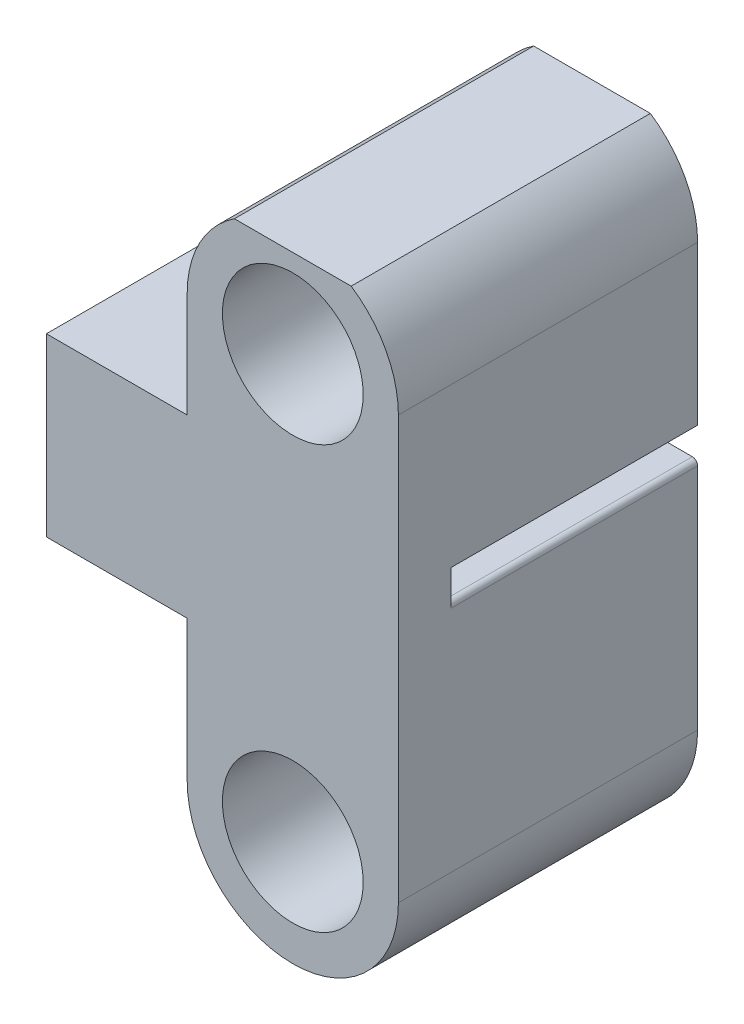
SolidWorks part; units mm, degrees
ref_plane "Front Plane" through (0, 0, 0) normal (0, 0, 1) x (1, 0, 0)
ref_plane "Top Plane" through (0, 0, 0) normal (0, 1, 0) x (1, 0, 0)
ref_plane "Right Plane" through (0, 0, 0) normal (1, 0, 0) x (0, 0, -1)
sketch "Sketch1" plane through (0, 0, 0) normal (0, 0, 1) x (1, 0, 0)
  line L0 (0, 0) -> (0, -12) construction
  line L1 (-3, 0) -> (-3, -12)
  line L2 (3, 0) -> (3, -12)
  arc A0 (3, 0) -> (-3, 0) centre (0, 0) ccw
  arc A1 (-3, -12) -> (3, -12) centre (0, -12) ccw
  circle A2 centre (0, 0) radius 2
  circle A3 centre (0, -12) radius 2
  dimension "D2" = 6
  dimension "D6" = 4
  dimension "D7" = 4
  dimension "D1" = 12
extrude "Boss-Extrude1" add sketch "Sketch1" along normal blind 8.5
sketch "Sketch2" plane through (3, 0, 0) normal (1, 0, 0) x (0, 0, -1)
  line L0 (-8.5, -6) -> (0, -6) construction
  line L1 (-8.5, -12) -> (-8.5, 0) construction
  line L2 (0, -12) -> (0, 0) construction
  line L3 (-4.25, 0) -> (-4.25, -12) construction
  line L4 (-8.5, 0) -> (0, 0) construction
  line L5 (-8.5, -12) -> (0, -12) construction
  circle A0 centre (-4.25, -8.5) radius 2
  dimension "D1" = 4
  dimension "D2" = 2.5
extrude "Cut-Extrude1" [suppressed] cut sketch "Sketch2" against normal through all
sketch "Sketch3" [suppressed] plane through (3, 0, 0) normal (1, 0, 0) x (0, 0, -1)
  line L1 (-0.6416, -8.5) -> (-2.4458, -5.375)
  line L2 (-2.4458, -5.375) -> (-6.0542, -5.375)
  line L3 (-6.0542, -5.375) -> (-7.8584, -8.5)
  line L4 (-7.8584, -8.5) -> (-6.0542, -11.625)
  line L5 (-6.0542, -11.625) -> (-2.4458, -11.625)
  line L6 (-2.4458, -11.625) -> (-0.6416, -8.5)
  line L7 (-1.8684, -4.375) -> (-6.6316, -4.375)
  line L8 (-6.6316, -4.375) -> (-9.0131, -8.5)
  line L9 (-9.0131, -8.5) -> (-6.6316, -12.625)
  line L10 (-6.6316, -12.625) -> (-1.8684, -12.625)
  line L11 (-1.8684, -12.625) -> (0.5131, -8.5)
  line L12 (0.5131, -8.5) -> (-1.8684, -4.375)
  circle A0 centre (-4.25, -8.5) radius 3.125 construction
  circle A1 centre (-4.25, -8.5) radius 4.125 construction
  dimension "D1" = 6.25
  dimension "D2" = 1
extrude "Boss-Extrude2" [suppressed] add sketch "Sketch3" along normal blind 2 and the other way blind 0.5
sketch "Sketch4" [suppressed] plane through (-3, 0, 0) normal (-1, 0, 0) x (0, 0, 1)
  line L0 (4.25, 0) -> (4.25, -6.5) construction
  line L1 (8.5, 0) -> (0, 0) construction
  line L3 (0.75, -2.75) -> (7.75, -2.75)
  line L4 (0.75, -2.75) -> (0.75, -5.75)
  line L5 (0.75, -5.75) -> (7.75, -5.75)
  line L6 (7.75, -2.75) -> (7.75, -5.75)
  line L7 (0.75, -2.75) -> (7.75, -5.75) construction
  line L8 (0.75, -5.75) -> (7.75, -2.75) construction
  circle A0 centre (4.25, -8.5) radius 2 construction
  point P7 (4.25, -4.25)
  dimension "D1" = 7
  dimension "D2" = 3
  dimension "D3" = 2.75
extrude "Cut-Extrude2" [suppressed] cut sketch "Sketch4" against normal through all
sketch "Sketch5" plane through (-3, 0, 0) normal (-1, 0, 0) x (0, 0, 1)
  line L0 (4.25, 0) -> (4.25, -12) construction
  line L1 (8.5, 0) -> (0, 0) construction
  line L2 (8.5, -12) -> (0, -12) construction
  line L3 (0, -6) -> (8.5, -6) construction
  line L4 (0, 0) -> (0, -12) construction
  line L5 (8.5, 0) -> (8.5, -12) construction
  line L7 (0, -15) -> (8.5, -15)
  line L8 (0, -15) -> (0, 3)
  line L9 (0, 3) -> (8.5, 3)
  line L10 (8.5, -15) -> (8.5, 3)
  line L11 (0, -15) -> (8.5, 3) construction
  line L12 (0, 3) -> (8.5, -15) construction
  point P12 (4.25, -6)
extrude "Cut-Extrude3" [suppressed] cut sketch "Sketch5" against normal through all flip side to cut
sketch "Sketch9" plane through (-3, 0, 0) normal (-1, 0, 0) x (0, 0, 1)
  line L0 (8.5, 0) -> (8.5, -12) construction
  line L1 (0, -3) -> (8.5, -3)
  line L2 (0, -3) -> (0, -8)
  line L3 (0, -8) -> (8.5, -8)
  line L4 (8.5, -3) -> (8.5, -8)
  line L5 (0, 0) -> (0, -12) construction
  line L6 (8.5, 0) -> (0, 0) construction
  dimension "D1" = 5
  dimension "D2" = 3
extrude "Boss-Extrude4" add sketch "Sketch9" along normal blind 4
sketch "Sketch6" plane through (3, 0, 0) normal (1, 0, 0) x (0, 0, -1)
  line L0 (0, -12) -> (0, 0) construction
  line L1 (0, -4.5) -> (-7, -4.5)
  line L2 (0, -4.5) -> (0, -6.1)
  line L3 (0, -6.1) -> (-7, -6.1)
  line L4 (-7, -4.5) -> (-7, -6.1)
  dimension "D1" = 1.6
  dimension "D2" = 4.5
  dimension "D3" = 7
extrude "Cut-Extrude5" cut sketch "Sketch6" against normal through all
sketch "Sketch7" plane through (0, 0, 7) normal (0, 0, -1) x (-1, 0, 0)
  line L0 (-3, -6.1) -> (-3, -5.5)
  line L1 (-3, -4.5) -> (-3, -6.1) construction
  line L2 (-2.85, -5.35) -> (-2.15, -5.35)
  line L3 (-2, -5.5) -> (-2, -6.1)
  line L4 (7, -6.1) -> (-3, -6.1) construction
  line L5 (-2, -6.1) -> (-3, -6.1)
  line L6 (-0.85, -5.35) -> (-0.15, -5.35)
  line L7 (0, -5.5) -> (0, -6.1)
  line L8 (0, -6.1) -> (-1, -6.1)
  line L9 (-1, -6.1) -> (-1, -5.5)
  line L10 (1.15, -5.35) -> (1.85, -5.35)
  line L11 (2, -5.5) -> (2, -6.1)
  line L12 (2, -6.1) -> (1, -6.1)
  line L13 (1, -6.1) -> (1, -5.5)
  line L14 (3.15, -5.35) -> (3.85, -5.35)
  line L15 (4, -5.5) -> (4, -6.1)
  line L16 (4, -6.1) -> (3, -6.1)
  line L17 (3, -6.1) -> (3, -5.5)
  line L18 (5.15, -5.35) -> (5.85, -5.35)
  line L19 (6, -5.5) -> (6, -6.1)
  line L20 (6, -6.1) -> (5, -6.1)
  line L21 (5, -6.1) -> (5, -5.5)
  arc A0 (-2.15, -5.35) -> (-2, -5.5) centre (-2.15, -5.5) cw
  arc A1 (-3, -5.5) -> (-2.85, -5.35) centre (-2.85, -5.5) cw
  arc A2 (-1, -5.5) -> (-0.85, -5.35) centre (-0.85, -5.5) cw
  arc A3 (-0.15, -5.35) -> (0, -5.5) centre (-0.15, -5.5) cw
  arc A4 (1, -5.5) -> (1.15, -5.35) centre (1.15, -5.5) cw
  arc A5 (1.85, -5.35) -> (2, -5.5) centre (1.85, -5.5) cw
  arc A6 (3, -5.5) -> (3.15, -5.35) centre (3.15, -5.5) cw
  arc A7 (3.85, -5.35) -> (4, -5.5) centre (3.85, -5.5) cw
  arc A8 (5, -5.5) -> (5.15, -5.35) centre (5.15, -5.5) cw
  arc A9 (5.85, -5.35) -> (6, -5.5) centre (5.85, -5.5) cw
  point P11 (-2, -5.35)
  point P14 (-3, -5.35)
  dimension "D3" = 0.15
  dimension "D1" = 1
  dimension "D2" = 0.75
  dimension "D4" = 5
extrude "Boss-Extrude3" add sketch "Sketch7" along normal through all
sketch "Sketch10" plane through (0, 0, 8.5) normal (0, 0, 1) x (1, 0, 0)
  line L1 (-2.5, 3.5) -> (2.5, 3.5)
  line L2 (-2.5, 3.5) -> (-2.5, 2.5)
  line L3 (-2.5, 2.5) -> (2.5, 2.5)
  line L4 (2.5, 3.5) -> (2.5, 2.5)
  line L5 (-2.5, 3.5) -> (2.5, 2.5) construction
  line L6 (-2.5, 2.5) -> (2.5, 3.5) construction
  arc A0 (3, 0) -> (-3, 0) centre (0, 0) ccw construction
  point P0 (0, 3)
  dimension "D1" = 1
  dimension "D2" = 5
extrude "Cut-Extrude6" cut sketch "Sketch10" against normal through all
equation "\"X-ROD-SPACING\"=45"
equation "\"Y-ROD-SPACING\"=75"
equation "\"Z-ROD-SPACING\"=17.5"
equation "\"Y-BED-OFFSET\"=2"
equation "\"Y-BED-ROD-INSET\"=3.5"
equation "\"Y-BED-SCREW-SPACING\"=209"
equation "\"Y-BED-SCREW-CUTOUT-SLOT-HEIGHT\"=2.5"
equation "\"T-SLOT-NUT-FILLET-RADIUS\"=0.5"
equation "\"T-SLOT-SCREW-SHAFT-RADIUS\"=1.55"
equation "\"T-SLOT-SCREW-SHAFT-CUTOUT-LENGTH\"=11"
equation "\"T-SLOT-NUT-DEPTH\"=3.5"
equation "\"T-SLOT-NUT-WIDTH\"=2.85"
equation "\"T-SLOT-NUT-END-DISTANCE\"=8"
equation "\"ACRYLIC-THICKNESS\"=10"
equation "\"ACRYLIC-THICKNESS2\"=4.5"
equation "\"ACRYLIC-TAB-CUTOUT-SIZE\"=\"ACRYLIC-THICKNESS\"+\"ACRYLIC-TAB-TOLERANCE\"*2"
equation "\"ACRYLIC-TAB-TOLERANCE\"=-.05"
equation "\"ACRYLIC-TAB-WIDTH\"=\"ACRYLIC-THICKNESS\""
equation "\"ACRYLIC-M3-HOLE\"=2.9"
equation "\"SMOOTHROD-CAP-SCREW-DISTANCE\"=20"
equation "\"FRAME-WIDTH-INNER\"=370"
equation "\"NEMA17-HOLE-SPACING\"=31"
equation "\"NEMA17-CENTRAL-CUTOUT\"=22.5"
equation "\"Z-BRACKET-REACH\"=57"
equation "\"Z-ROD-INSET\"=13.5"
equation "\"TOP-BRACKET-SPACING\"=40"
equation "\"SMOOTHROD-X-LENGTH\"=350"
equation "\"SMOOTHROD-Y-LENGTH\"=350"
equation "\"SMOOTHROD-Z-LENGTH\"=350"
equation "\"SMOOTHROD-TIGHTENING-HEADROOM\"=.25"
equation "\"LEADSCREW-Z-LENGTH\"=300"
equation "\"SCREW-LENGTH-FRAME\"=\"ACRYLIC-THICKNESS\" + 10"
equation "\"SCREW-LENGTH-MOTOR\"=\"ACRYLIC-THICKNESS\" + 5"
equation "\"SCREW-LENGTH-EXTRUDER\"=28"
equation "\"SCREW-HEAD-RADIUS\"=6"
equation "\"PRINTED-M3-HOLE\"=3.5"
equation "\"PRINTED-X-SMOOTHROD-DIAMETER\"=8.8"
equation "\"PRINTED-X-SMOOTHROD-CUTOUT\"=10"
equation "\"PRINTED-X-BASE-HEIGHT\"=10"
equation "\"PRINTED-LM8UU-CUTOUT-SIZE\"=15.5"
equation "\"PRINTED-LM8UU-CUTOUT-LENGTH\"=24.5"
equation "\"PRINTED-X-IDLER-HEIGHT\"=16"
equation "\"PRINTED-M3-NUT-AF\"=6.25"
equation "\"PSU-MOUNTING-WIDTH\"=95"
equation "\"PSU-MOUNTING-HEIGHT\"=177"
equation "\"Y-BELT-TO-ROD-DISTANCE\"=20"
equation "\"SPOOL-HOLDER-ROD-SPACING\"=150"
equation "\"ACRYLIC-X-CARRIAGE-WIDTH\"=55"
equation "\"ACRYLIC-X-CARRIAGE-HEIGHT\"=75"
equation "\"ACRYLIC-X-CARRIAGE-LM8UU-CUTOUT-WIDTH\"=24.25"
equation "\"ACRYLIC-X-CARRIAGE-LM8UU-CUTOUT-HEIGHT\"=11.0"
equation "\"ACRYLIC-X-CARRIAGE-SCREW-SPACING-X\"=15"
equation "\"ACRYLIC-X-CARRIAGE-SCREW-SPACING-Y\"=33"
equation "\"ACRYLIC-X-CARRIAGE-CENTER-TAB-SPACING\"=14"
equation "\"ACRYLIC-X-CARRIAGE-EXTRUDER-OFFSET\"=26"
equation "\"ACRYLIC-X-CARRIAGE-EXTRUDER-ANGLE\"=90"
equation "\"ACRYLIC-X-CARRIAGE-EXTRUDER-SHELF-DEPTH\"=\"ACRYLIC-X-CARRIAGE-EXTRUDER-OFFSET\" + 28"
equation "\"ACRYLIC-X-CARRIAGE-EXTRUDER-BRACE-SPACING\"=23"
equation "\"ACRYLIC-X-CARRIAGE-EXTRUDER-BRACE-TAB-OFFSET\"=20"
equation "\"ACRYLIC-X-CARRIAGE-EXTRUDER-BRACE-HEIGHT\"=35"
equation "\"ACRYLIC-X-CARRIAGE-EXTRUDER-BRACE-SCREW-SPACING\"=22"
equation "\"ACRYLIC-X-CARRIAGE-DUAL-WIDTH-MULTIPLIER\"=1.65"
equation "\"ACRYLIC-X-CARRIAGE-DUAL-HOTEND-SPACING\"=42"
equation "\"ACRYLIC-X-CARRIAGE-DUAL-WIDTH\"=75"
equation "\"ACRYLIC-X-CARRIAGE-DUAL-HOTEND-SEPARATION\"=36"
equation "\"ACRYLIC-X-CARRIAGE-DUAL-MOUNT-PLATE-DEPTH\"=75"
equation "\"ACRYLIC-X-CARRIAGE-DUAL-MOUNT-BRACE-WIDTH\"=33"
equation "\"ACRYLIC-X-CARRIAGE-DUAL-MOUNT-SCREW-WIDTH\"=40"
equation "\"BLOWER-FAN-WIDTH\"=15"
equation "\"D1@Sketch3\"=\"PRINTED-M3-NUT-AF\""
